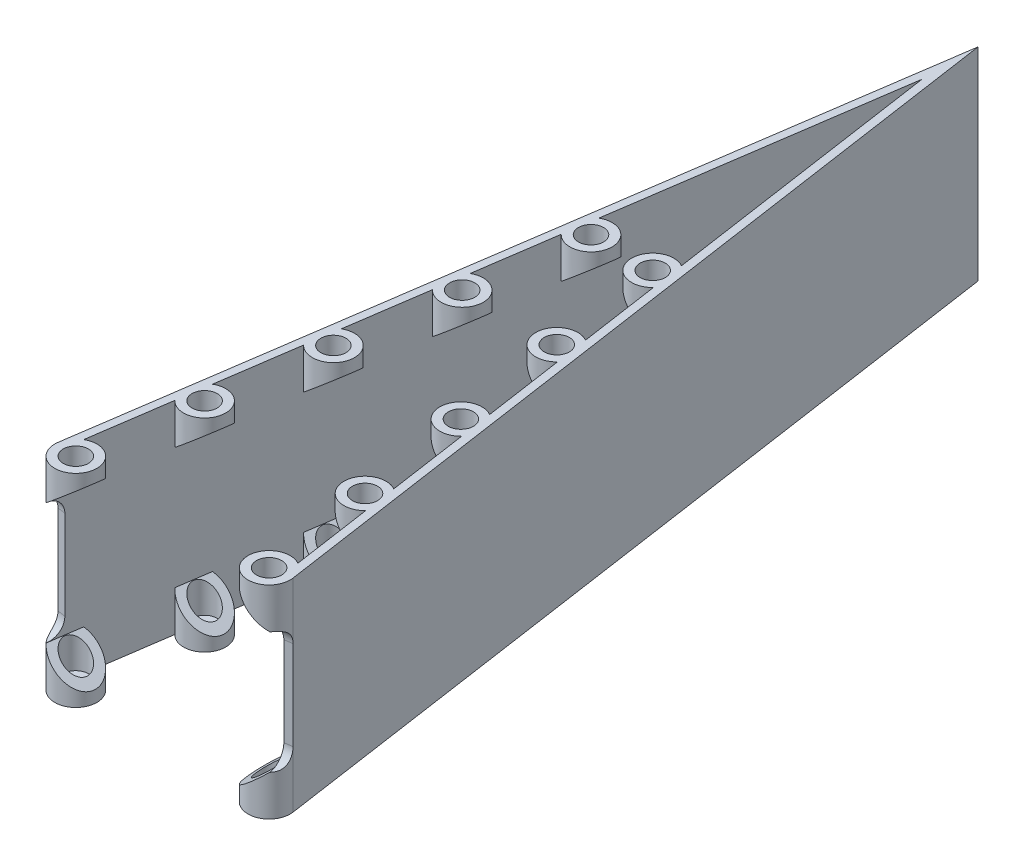
SolidWorks part; units mm, degrees
ref_plane "Front Plane" through (0, 0, 0) normal (0, 0, 1) x (1, 0, 0)
ref_plane "Top Plane" through (0, 0, 0) normal (0, 1, 0) x (1, 0, 0)
ref_plane "Right Plane" through (0, 0, 0) normal (1, 0, 0) x (0, 0, -1)
sketch "Sketch1" plane through (0, 0, 0) normal (0, 1, 0) x (1, 0, 0)
  line L0 (-13.5, 0) -> (13.5, 0) construction
  line L1 (-13.5, 0) -> (0, 92.188)
  line L2 (0, 92.188) -> (13.5, 0)
  line L3 (13.5, 0) -> (14.4894, 0.1449)
  line L4 (14.4894, 0.1449) -> (0, 99.0896)
  line L5 (0, 99.0896) -> (-14.4894, 0.1449)
  line L6 (-14.4894, 0.1449) -> (-13.5, 0)
  point P2 (0, 0)
  dimension "D1" = 90
  dimension "D2" = 90
  dimension "D4" = 1
  dimension "D3" = 100
  dimension "D5" = 27
extrude "Boss-Extrude1" add sketch "Sketch1" along normal blind 25
sketch "Sketch2" plane through (0, 0, 0) normal (0, 1, 0) x (1, 0, 0)
  line L0 (0, -1000) -> (0, 49000) construction
  line L1 (0, 92.188) -> (13.5, 0) construction
  line L2 (0, 92.188) -> (13.5, 0) construction
  line L3 (11.9169, -0.2318) -> (13.5, 0) construction
  line L4 (13.5, 0) -> (14.4894, 0.1449) construction
  line L5 (14.4894, 0.1449) -> (0, 99.0896) construction
  line L6 (14.4894, 0.1449) -> (0, 99.0896) construction
  circle A0 centre (11.9169, -0.2318) radius 2.6
  circle A1 centre (11.9169, -0.2318) radius 1.55
  circle A2 centre (9.8884, 13.6204) radius 1.55
  circle A3 centre (9.8884, 13.6204) radius 2.6
  circle A4 centre (7.8598, 27.4727) radius 1.55
  circle A5 centre (7.8598, 27.4727) radius 2.6
  circle A6 centre (5.8313, 41.3249) radius 1.55
  circle A7 centre (5.8313, 41.3249) radius 2.6
  circle A8 centre (3.8028, 55.1772) radius 1.55
  circle A9 centre (3.8028, 55.1772) radius 2.6
  circle A12 centre (-11.9169, -0.2318) radius 2.6
  circle A13 centre (-11.9169, -0.2318) radius 1.55
  circle A14 centre (-9.8884, 13.6204) radius 2.6
  circle A15 centre (-9.8884, 13.6204) radius 1.55
  circle A16 centre (-7.8598, 27.4727) radius 2.6
  circle A17 centre (-7.8598, 27.4727) radius 1.55
  circle A18 centre (-5.8313, 41.3249) radius 2.6
  circle A19 centre (-5.8313, 41.3249) radius 1.55
  circle A20 centre (-3.8028, 55.1772) radius 2.6
  circle A21 centre (-3.8028, 55.1772) radius 1.55
  dimension "D1" = 5.2
  dimension "D2" = 3.1
  dimension "D4" = 14
  dimension "D3" = 5
extrude "Boss-Extrude3" add sketch "Sketch2" along normal blind 5
sketch "Sketch4" plane through (0.2834, 0, 1.9354) normal (0.1449, 0, 0.9894) x (0.9894, 0, -0.1449)
  line L0 (9.1575, 5) -> (9.1575, 0) construction
  line L1 (14.3575, 5) -> (9.1575, 5) construction
  line L2 (13.3575, 25) -> (13.3575, 0) construction
  line L3 (9.1575, 5) -> (9.1575, 0) construction
  line L4 (14.3575, 5) -> (9.1575, 5) construction
  line L5 (13.3575, 25) -> (13.3575, 0) construction
  line L6 (13.3575, 5) -> (9.1575, 1.4758)
  line L7 (13.3575, 5) -> (9.1575, 5)
  line L8 (9.1575, 5) -> (9.1575, 1.4758)
  dimension "D1" = 40
extrude "Cut-Extrude1" cut sketch "Sketch4" against normal up to surface and the other way through all contours L7 L8 L6 region at (10.7295, 3.8253, 0.4057) up to face at (-8.5575, 4.5455, -33.751)
sketch "Sketch5" plane through (-0.2834, 0, 1.9354) normal (-0.1449, 0, 0.9894) x (0.9894, 0, 0.1449)
  line L0 (-9.1575, 0) -> (-9.1575, 5) construction
  line L1 (-9.1575, 5) -> (-14.3575, 5) construction
  line L2 (-13.3575, 25) -> (-13.3575, 0) construction
  line L3 (-9.1575, 0) -> (-9.1575, 5) construction
  line L4 (-9.1575, 5) -> (-14.3575, 5) construction
  line L5 (-13.3575, 25) -> (-13.3575, 0) construction
  line L6 (-13.3575, 5) -> (-9.1575, 1.4758)
  line L7 (-13.3575, 5) -> (-9.1575, 5)
  line L8 (-9.1575, 5) -> (-9.1575, 1.4758)
  dimension "D1" = 40
extrude "Cut-Extrude2" cut sketch "Sketch5" against normal up to surface and the other way through all contours L8 L7 L6 region at (-10.7295, 3.8253, 0.4057) up to face at (8.5575, 4.5455, -33.751)
ref_plane "Plane1" through (0, 12.5, 0) normal (0, 1, 0) x (1, 0, 0)
mirror "Mirror2" about plane through (0, 12.5, 0) normal (0, 1, 0) of "Cut-Extrude2", "Cut-Extrude1", "Boss-Extrude3"
fillet "Fillet1" radius 2 4 edges at (-13.9947, 5, -0.0724) (13.9947, 5, -0.0724) (13.9947, 20, -0.0724) (-13.9947, 20, -0.0724)
sketch "Sketch6" plane through (0, 0, 0) normal (0, -1, 0) x (1, 0, 0)
  arc A0 (-13.2031, -2.0278) -> (-14.4894, -0.1449) centre (-11.9169, 0.2318) ccw construction
  arc A1 (14.4894, -0.1449) -> (13.2031, -2.0278) centre (11.9169, 0.2318) ccw construction
  arc A2 (11.7684, -11.8245) -> (11.1745, -15.88) centre (9.8884, -13.6204) ccw construction
  arc A3 (-11.1745, -15.88) -> (-11.7684, -11.8245) centre (-9.8884, -13.6204) ccw construction
  arc A4 (-9.146, -29.7323) -> (-9.7399, -25.6768) centre (-7.8598, -27.4727) ccw construction
  arc A5 (9.7399, -25.6768) -> (9.146, -29.7323) centre (7.8598, -27.4727) ccw construction
  arc A6 (7.7114, -39.529) -> (7.1175, -43.5845) centre (5.8313, -41.3249) ccw construction
  arc A7 (-7.1175, -43.5845) -> (-7.7114, -39.529) centre (-5.8313, -41.3249) ccw construction
  arc A8 (-5.089, -57.4368) -> (-5.6829, -53.3813) centre (-3.8028, -55.1772) ccw construction
  arc A9 (5.6829, -53.3813) -> (5.089, -57.4368) centre (3.8028, -55.1772) ccw construction
  arc A10 (-13.2031, -2.0278) -> (-14.4894, -0.1449) centre (-11.9169, 0.2318) ccw
  arc A11 (14.4894, -0.1449) -> (13.2031, -2.0278) centre (11.9169, 0.2318) ccw
  arc A12 (11.7684, -11.8245) -> (11.1745, -15.88) centre (9.8884, -13.6204) ccw
  arc A13 (-11.1745, -15.88) -> (-11.7684, -11.8245) centre (-9.8884, -13.6204) ccw
  arc A14 (-9.146, -29.7323) -> (-9.7399, -25.6768) centre (-7.8598, -27.4727) ccw
  arc A15 (9.7399, -25.6768) -> (9.146, -29.7323) centre (7.8598, -27.4727) ccw
  arc A16 (7.7114, -39.529) -> (7.1175, -43.5845) centre (5.8313, -41.3249) ccw
  arc A17 (-7.1175, -43.5845) -> (-7.7114, -39.529) centre (-5.8313, -41.3249) ccw
  arc A18 (-5.089, -57.4368) -> (-5.6829, -53.3813) centre (-3.8028, -55.1772) ccw
  arc A19 (5.6829, -53.3813) -> (5.089, -57.4368) centre (3.8028, -55.1772) ccw
  circle A20 centre (3.8028, -55.1772) radius 2.6
  circle A21 centre (-3.8028, -55.1772) radius 2.6
  circle A22 centre (5.8313, -41.3249) radius 2.6
  circle A23 centre (-5.8313, -41.3249) radius 2.6
  circle A24 centre (7.8598, -27.4727) radius 2.6
  circle A25 centre (-7.8598, -27.4727) radius 2.6
  circle A26 centre (-9.8884, -13.6204) radius 2.6
  circle A27 centre (9.8884, -13.6204) radius 2.6
  circle A28 centre (11.9169, 0.2318) radius 2.6
  circle A29 centre (-11.9169, 0.2318) radius 2.6
  circle M23 centre (11.9169, 0.2318) radius 1.55
  circle M24 centre (9.8884, -13.6204) radius 1.55
  circle M25 centre (7.8598, -27.4727) radius 1.55
  circle M26 centre (5.8313, -41.3249) radius 1.55
  circle M27 centre (3.8028, -55.1772) radius 1.55
  circle M28 centre (-5.8313, -41.3249) radius 1.55
  circle M29 centre (-9.8884, -13.6204) radius 1.55
  circle M30 centre (-11.9169, 0.2318) radius 1.55
  circle M31 centre (-7.8598, -27.4727) radius 1.55
  circle M32 centre (-3.8028, -55.1772) radius 1.55
extrude "Boss-Extrude4" add sketch "Sketch6" against normal blind 1 contours M27 | M32 | M28 | M26 | M25 | M31 | M29 | M24 | M23 | M30 region at (11.9169, 0, 0.2318) region at (9.8884, 0, -13.6204) region at (7.8598, 0, -27.4727) region at (5.8313, 0, -41.3249) region at (3.8028, 0, -55.1772) region at (-5.8313, 0, -41.3249) region at (-9.8884, 0, -13.6204) region at (-11.9169, 0, 0.2318) region at (-7.8598, 0, -27.4727) region at (-3.8028, 0, -55.1772)
equation "\"D2@Sketch1\"=\"D1@Sketch1\""
